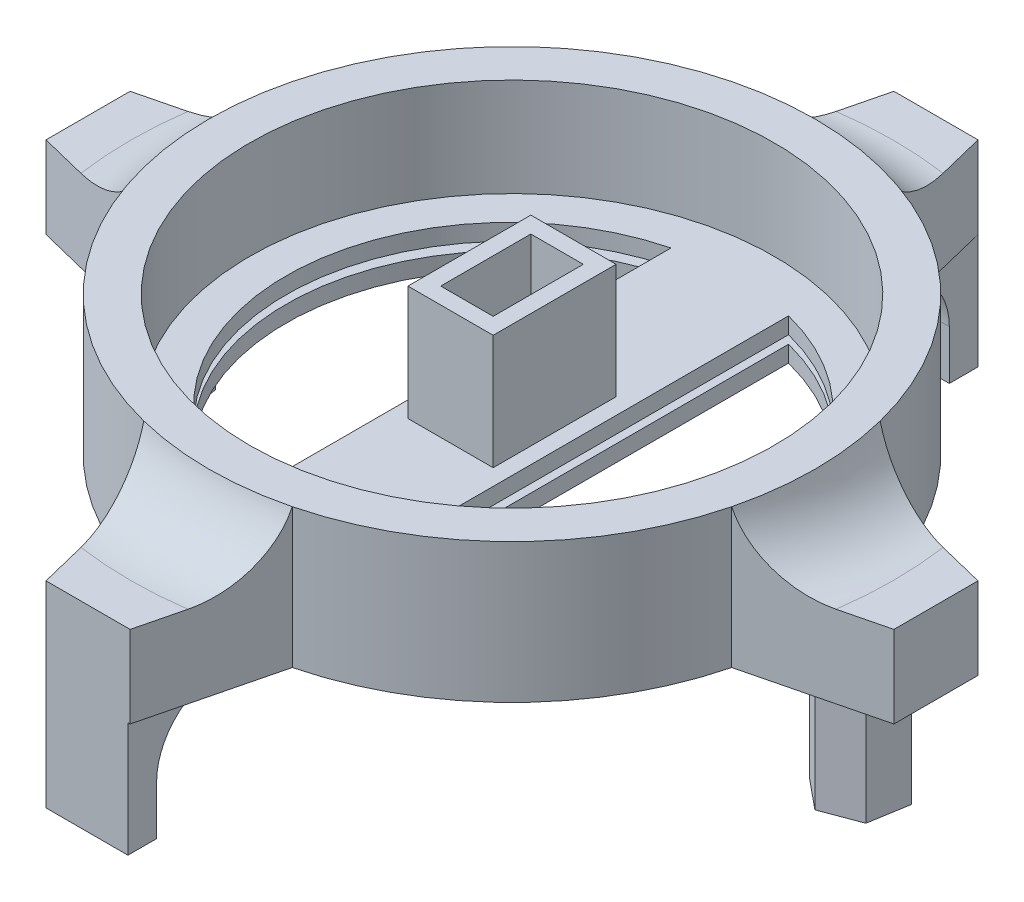
SolidWorks part; units mm, degrees
other "Markup1"
sketch "Sketch14" plane through (-25.8693, -8.5, 20.9211) normal (0, -1, 0) x (1, 0, 0)
other "Markup2"
sketch "Sketch15" plane through (-25.8693, -8.5, 20.9211) normal (0, -1, 0) x (1, 0, 0)
ref_plane "Front Plane" through (0, 0, 0) normal (0, 0, 1) x (1, 0, 0)
ref_plane "Top Plane" through (0, 0, 0) normal (0, 1, 0) x (1, 0, 0)
ref_plane "Right Plane" through (0, 0, 0) normal (1, 0, 0) x (0, 0, -1)
sketch "Sketch4" plane through (0, 0, 0) normal (0, 1, 0) x (1, 0, 0)
  line L0 (0, -46.7905) -> (24.3942, -46.7905) construction
  line L1 (0, -46.7905) -> (0, -24.9936) construction
  circle A0 centre (0, -46.7905) radius 17
  dimension "D1" = 34
extrude "Boss-Extrude3" add sketch "Sketch4" along normal blind 6 separate body
shell "Shell4" thickness 0.5 removed face at (0, 6, 63.7905) outward yes
ref_plane "Plane2" through (0, 0, 0) normal (0, 1, 0) x (1, 0, 0)
sketch "Sketch5" plane through (0, 0, 0) normal (0, 1, 0) x (1, 0, 0)
  line L0 (17, -46.7905) -> (-25.0436, -46.7905) construction
  line L1 (1.6, -44.0405) -> (-1.6, -44.0405)
  line L2 (1.6, -44.0405) -> (1.6, -49.5405)
  line L3 (1.6, -49.5405) -> (-1.6, -49.5405)
  line L4 (-1.6, -44.0405) -> (-1.6, -49.5405)
  line L5 (0, -29.7905) -> (0, -85.3723) construction
  circle A0 centre (0, -46.7905) radius 17 construction
  circle A1 centre (0, -46.7905) radius 17 construction
  dimension "D1" = 5.5
  dimension "D2" = 3.2
  dimension "D3" = 2.75
  dimension "D4" = 1.6
extrude "Boss-Extrude4" add sketch "Sketch5" along normal blind 8
shell "Shell5" thickness 1 removed face at (0, 8, 46.7905) outward yes
sketch "Sketch6" plane through (0, 0, 0) normal (0, 1, 0) x (1, 0, 0)
  line L1 (-2.5652, -72.6598) -> (2.5652, -72.6598)
  line L2 (2.5652, -72.6598) -> (4.5312, -64.727)
  line L3 (-2.5652, -72.6598) -> (-4.5312, -64.727)
  line L4 (-25.8693, -44.2252) -> (-17.9365, -42.2592)
  line L5 (-25.8693, -49.3557) -> (-17.9365, -51.3217)
  line L6 (-25.8693, -44.2252) -> (-25.8693, -49.3557)
  line L7 (2.5652, -20.9211) -> (4.5312, -28.854)
  line L8 (-2.5652, -20.9211) -> (-4.5312, -28.854)
  line L9 (2.5652, -20.9211) -> (-2.5652, -20.9211)
  line L10 (25.8693, -49.3557) -> (17.9365, -51.3217)
  line L11 (25.8693, -44.2252) -> (17.9365, -42.2592)
  line L12 (25.8693, -49.3557) -> (25.8693, -44.2252)
  circle A0 centre (0, -46.7905) radius 18.5 construction
  arc A1 (4.5312, -64.727) -> (-4.5312, -64.727) centre (0, -46.7905) cw
  arc A2 (-17.9365, -51.3217) -> (-17.9365, -42.2592) centre (0, -46.7905) cw
  arc A3 (-4.5312, -28.854) -> (4.5312, -28.854) centre (0, -46.7905) cw
  arc A4 (17.9365, -42.2592) -> (17.9365, -51.3217) centre (0, -46.7905) cw
  point P22 (0, -46.7905)
  dimension "D1" = 4
extrude "Boss-Extrude6" add sketch "Sketch6" against normal up to surface (1.5 mm away) and the other way blind 3.5 up to face at (0, -1.5, 65.2905)
sketch "Sketch7" plane through (0, -1.5, 0) normal (0, -1, 0) x (-1, 0, 0)
  line L0 (0, -20.9211) -> (0, -83.0743) construction
  line L1 (2.5652, -72.6598) -> (-2.4348, -72.6598)
  line L2 (2.5652, -72.6598) -> (2.5652, -70.9098)
  line L3 (2.5652, -70.9098) -> (-2.4348, -70.9098)
  line L4 (-2.4348, -72.6598) -> (-2.4348, -70.9098)
  line L5 (2.5652, -20.9211) -> (-2.5652, -20.9211) construction
  line L6 (25.8693, -46.7905) -> (-32.5376, -46.7905) construction
  line L7 (25.8693, -49.3557) -> (25.8693, -44.2252) construction
  line L12 (-2.5652, -20.9211) -> (-2.5652, -22.6711)
  line L13 (-2.5652, -20.9211) -> (2.4348, -20.9211)
  line L14 (2.4348, -20.9211) -> (2.4348, -22.6711)
  line L15 (-2.5652, -22.6711) -> (2.4348, -22.6711)
  line L20 (25.8693, -44.2252) -> (24.1193, -44.2252) [skipped]
  line L21 (24.1193, -44.2252) -> (24.1193, -49.2252) [skipped]
  line L22 (25.8693, -49.2252) -> (24.1193, -49.2252) [skipped]
  line L23 (25.8693, -44.2252) -> (25.8693, -49.2252) [skipped]
  line L24 (-25.8693, -49.3557) -> (-24.1193, -49.3557) [skipped]
  line L25 (-24.1193, -49.3557) -> (-24.1193, -44.3557) [skipped]
  line L26 (-25.8693, -44.3557) -> (-24.1193, -44.3557) [skipped]
  line L27 (-25.8693, -49.3557) -> (-25.8693, -44.3557) [skipped]
  point P14 (0, -46.7905)
  point P30 (0, -46.7905)
  dimension "D1" = 5
  dimension "D2" = 1.75
  dimension "D3" = 4
extrude "Boss-Extrude7" add sketch "Sketch7" along normal blind 7
fillet "Fillet3" radius 5 4 edges at (0, 3.5, 65.2905) (-18.5, 3.5, 46.7905) (18.5, 3.5, 46.7905) (0, 3.5, 28.2905)
sketch "Sketch11" plane through (0, 1, 0) normal (0, 1, 0) x (1, 0, 0)
  line L0 (-3.5859, -59.9216) -> (-3.5859, -33.5012)
  line L1 (0, -44.0405) -> (0, -17.5543) construction
  line L2 (1.6, -44.0405) -> (-1.6, -44.0405) construction
  line L3 (3.5859, -59.9216) -> (3.5859, -33.5012)
  arc A0 (-3.5859, -59.9216) -> (-3.5859, -33.5012) centre (-0.2324, -46.7114) cw
  arc A1 (3.5859, -59.9216) -> (3.5859, -33.5012) centre (0.2324, -46.7114) ccw
extrude "Cut-Extrude1" cut sketch "Sketch11" against normal blind 5
sketch "Sketch13" plane through (0, -0.5, 0) normal (0, 1, 0) x (1, 0, 0)
  line L1 (-1.566, -49.504) -> (1.6, -49.504)
  line L2 (-1.566, -49.504) -> (-1.566, -44.0405)
  line L3 (-1.566, -44.0405) -> (1.6, -44.0405)
  line L4 (1.6, -49.504) -> (1.6, -44.0405)
extrude "Cut-Extrude2" cut sketch "Sketch13" against normal blind 5
fillet "Fillet4" radius 4 2 edges at (0.0652, -1.5, 22.6711) (-0.0652, -1.5, 70.9098)
sketch "Sketch16" plane through (0, -1.5, 0) normal (0, -1, 0) x (-1, 0, 0)
  line L0 (-0.017, -49.504) -> (-0.017, -17.3421) construction
  line L1 (19.0951, -47.7692) -> (20.962, -49.3051)
  line L2 (20.962, -49.3051) -> (23.2256, -48.4562)
  line L3 (23.2256, -48.4562) -> (23.6223, -46.0715)
  line L4 (23.6223, -46.0715) -> (21.7554, -44.5356)
  line L5 (21.7554, -44.5356) -> (19.4918, -45.3844)
  line L6 (19.4918, -45.3844) -> (19.0951, -47.7692)
  line L7 (1.566, -49.504) -> (-1.6, -49.504) construction
  line L8 (-19.5258, -45.3844) -> (-19.1291, -47.7692)
  line L9 (-21.7893, -44.5356) -> (-19.5258, -45.3844)
  line L10 (-23.6563, -46.0715) -> (-21.7893, -44.5356)
  line L11 (-23.2596, -48.4562) -> (-23.6563, -46.0715)
  line L12 (-20.996, -49.3051) -> (-23.2596, -48.4562)
  line L13 (-19.1291, -47.7692) -> (-20.996, -49.3051)
  circle A0 centre (21.3587, -46.9203) radius 2.0936 construction
  point P18 (20.8324, -46.9203)
  point P19 (21.3587, -46.9203)
extrude "Boss-Extrude8" add sketch "Sketch16" along normal blind 7
